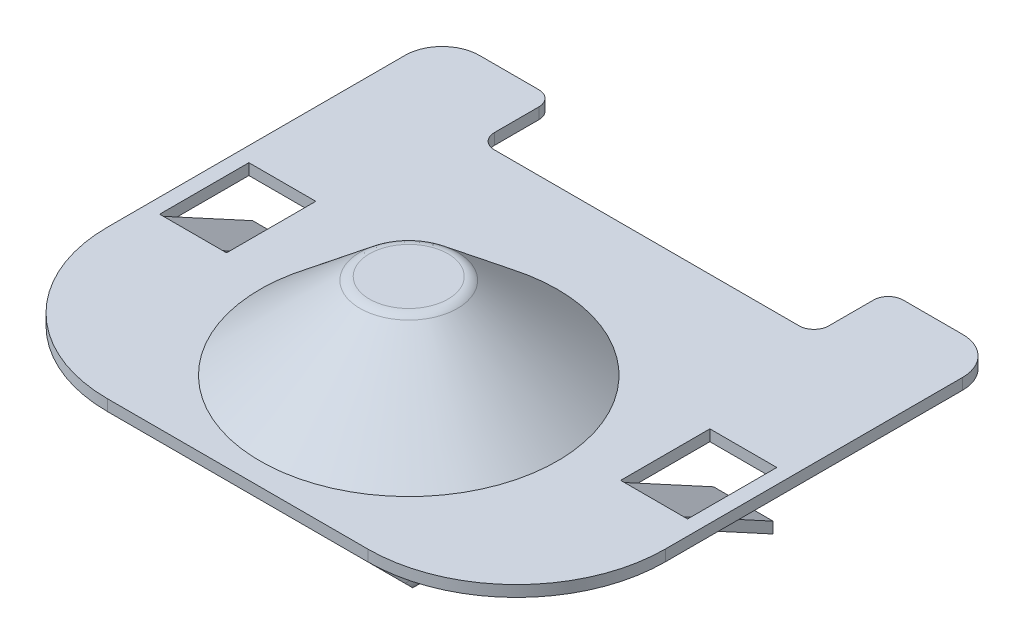
SolidWorks part; units mm, degrees
material "Plain Carbon Steel"
ref_plane "Front Plane" through (0, 0, 0) normal (0, 0, 1) x (1, 0, 0)
ref_plane "Top Plane" through (0, 0, 0) normal (0, 1, 0) x (1, 0, 0)
ref_plane "Right Plane" through (0, 0, 0) normal (1, 0, 0) x (0, 0, -1)
sketch "Sketch1" plane through (0, 0, 0) normal (0, 1, 0) x (1, 0, 0)
  line L1 (-7.5, 6.5) -> (7.5, 6.5)
  line L2 (-7.5, 6.5) -> (-7.5, -6.5)
  line L3 (-7.5, -6.5) -> (7.5, -6.5)
  line L4 (7.5, 6.5) -> (7.5, -6.5)
  line L5 (-7.5, 6.5) -> (7.5, -6.5) construction
  line L6 (-7.5, -6.5) -> (7.5, 6.5) construction
  point P0 (0, 0)
  dimension "D1" = 15
  dimension "D2" = 13
extrude "BASE" add sketch "Sketch1" along normal blind 0.3
sketch "Sketch2" plane through (0, 0.3, 0) normal (0, 1, 0) x (1, 0, 0)
  line L1 (0, -6.5) -> (0, -1.9) construction
  line L2 (-7.5, -6.5) -> (7.5, -6.5) construction
  circle A0 centre (0, -1.9) radius 4
  dimension "D1" = 8
  dimension "D3" = 4.6
extrude "PT CUT" cut sketch "Sketch2" against normal through all
ref_axis "POSITIVE" through (0, 0, 1.9) along (0, 1, 0)
ref_plane "PT REFERENCE PLANE" through (0, 0, 1.9) normal (0, 0, 1) x (1, 0, 0)
sketch "Sketch4" plane through (0, 0, 1.9) normal (0, 0, 1) x (1, 0, 0)
  line L0 (0, 2.6) -> (1.0568, 2.6)
  line L2 (4, 0) -> (3.7, 0)
  line L4 (1.0936, 2.3) -> (0, 2.3)
  line L5 (0, 2.3) -> (0, 2.6)
  line L6 (-4, 0) -> (4, 0) construction
  line L7 (4, 0) -> (4, 0.3) construction
  line L8 (1.3107, 2.5091) -> (4, 0.3)
  line L9 (4, 0.3) -> (-4, 0.3) construction
  line L10 (4, 0) -> (4, 0.3)
  line L11 (0, 0) -> (0, 0.3) construction
  line L12 (3.6, 0.1) -> (3.6, 0.2527)
  line L13 (3.5635, 0.33) -> (1.2206, 2.2545)
  line L14 (-7.5, 0) -> (7.5, 0) construction
  line L15 (3.6, 0.3) -> (4, 0.3) construction
  arc A0 (1.0936, 2.3) -> (1.2206, 2.2545) centre (1.0936, 2.1) cw
  arc A1 (1.3107, 2.5091) -> (1.0568, 2.6) centre (1.0568, 2.2) ccw
  arc A2 (3.6, 0.1) -> (3.7, 0) centre (3.7, 0.1) ccw
  arc A3 (3.5635, 0.33) -> (3.6, 0.2527) centre (3.5, 0.2527) cw
  point P22 (1.2, 2.6)
  dimension "D4" = 0.2
  dimension "D5" = 0.4
  dimension "D6" = 0.1
  dimension "D7" = 0.1
  dimension "D1" = 0.3
  dimension "D2" = 1.2
  dimension "D3" = 2.6
revolve "POSITIVE TERMINAL" add sketch "Sketch4" angle 360 about axis through (0, 0, 1.9) along (0, 1, 0)
sketch "Sketch5" plane through (0, 0, 0) normal (1, 0, 0) x (0, 0, -1)
  line L0 (-6.5, 0) -> (-2.5, -4)
  line L1 (-6.5, 0.3) -> (-6.5, 0) construction
  line L2 (-6.5, 0) -> (-6.2, 0)
  line L3 (-6.2, 0) -> (-2.2, -4)
  line L4 (-2.2, -4) -> (-2.5, -4)
  dimension "D1" = 45
  dimension "D2" = 4
  dimension "D3" = 0.3
extrude "WIRE CONNECTION" add sketch "Sketch5" along normal mid plane 2
sketch "Sketch7" plane through (0, 0.3, 0) normal (0, 1, 0) x (1, 0, 0)
  line L0 (-7.5, -6.5) -> (7.5, -6.5) construction
  line L1 (5.3, 0.9) -> (7.1, 0.9)
  line L2 (5.3, 0.9) -> (5.3, -1.5)
  line L3 (5.3, -1.5) -> (7.1, -1.5)
  line L4 (7.1, 0.9) -> (7.1, -1.5)
  line L5 (5.3, 0.9) -> (7.1, -1.5) construction
  line L6 (5.3, -1.5) -> (7.1, 0.9) construction
  line L7 (7.5, -6.5) -> (7.5, 6.5) construction
  point P0 (6.2, -0.3)
  dimension "D1" = 2.4
  dimension "D2" = 1.8
  dimension "D3" = 5
  dimension "D4" = 0.4
extrude "LOCKING CLAMP CUT" cut sketch "Sketch7" against normal through all
ref_plane "LCC REFERENCE PLANE" through (6.2, 0, 0) normal (1, 0, 0) x (0, 0, -1)
sketch "Sketch8" plane through (6.2, 0, 0) normal (1, 0, 0) x (0, 0, -1)
  line L0 (0.9, -1) -> (-1.5, 0.3)
  line L1 (-1.5, 0.3) -> (-1.5, 0)
  line L2 (-1.5, 0) -> (0.9, -1.3)
  line L3 (0.9, -1.3) -> (0.9, -1)
  line L4 (0.9, 0) -> (0.9, 0.3) construction
  dimension "D1" = 1.6
extrude "LOCKING CLAMP" add sketch "Sketch8" along normal mid plane 1.6
mirror "LC M" about plane through (0, 0, 0) normal (1, 0, 0) of "LOCKING CLAMP", "LOCKING CLAMP CUT"
sketch "Sketch9" plane through (0, 0.3, 0) normal (0, 1, 0) x (1, 0, 0)
  line L0 (7.5, 6.5) -> (-7.5, 6.5) construction
  line L1 (-4.5, 4.5) -> (4.5, 4.5)
  line L2 (-4.5, 4.5) -> (-4.5, 6.5)
  line L3 (-4.5, 6.5) -> (4.5, 6.5)
  line L4 (4.5, 4.5) -> (4.5, 6.5)
  line L5 (-4.5, 4.5) -> (4.5, 6.5) construction
  line L6 (-4.5, 6.5) -> (4.5, 4.5) construction
  line L7 (0, 0) -> (0, 5.5) construction
  point P0 (0, 5.5)
  dimension "D1" = 9
  dimension "D2" = 2
extrude "BOTTOM SLOT CUT" cut sketch "Sketch9" against normal through all
fillet "TS F" radius 1 2 edges at (-7.5, 0.15, -6.5) (7.5, 0.15, -6.5)
fillet "BS F" radius 4 2 edges at (7.5, 0.15, 6.5) (-7.5, 0.15, 6.5)
fillet "WC F" radius 0.5 2 edges at (-1, -4, 2.35) (1, -4, 2.35)
fillet "BSC F" radius 0.4 4 edges at (4.5, 0.15, -6.5) (4.5, 0.15, -4.5) (-4.5, 0.15, -4.5) (-4.5, 0.15, -6.5)
